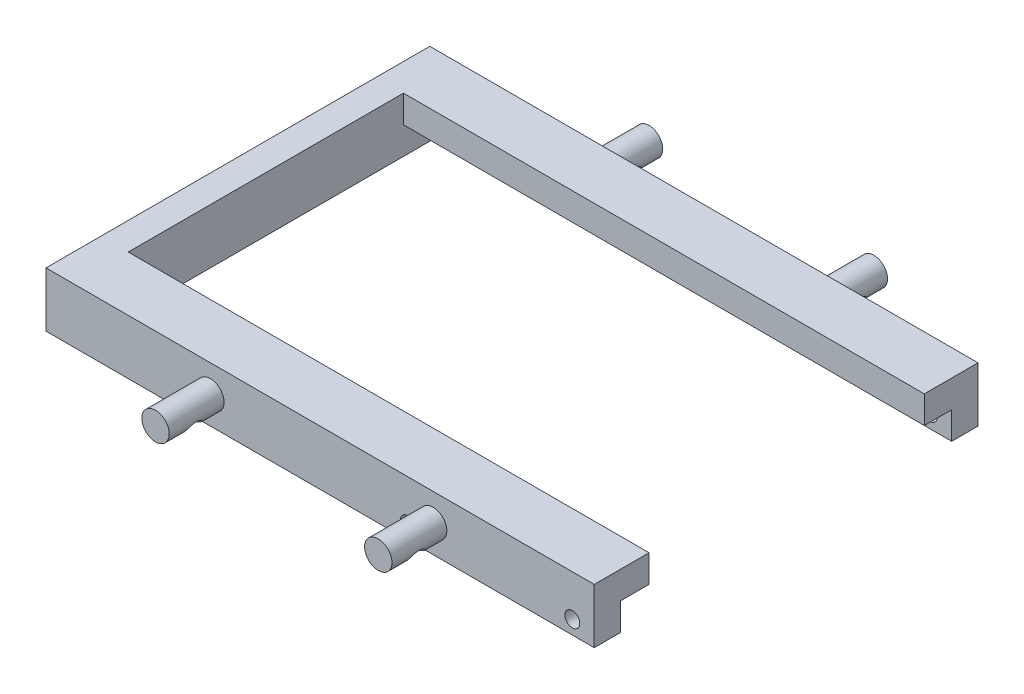
SolidWorks part; units mm, degrees
ref_plane "Front Plane" through (0, 0, 0) normal (0, 0, 1) x (1, 0, 0)
ref_plane "Top Plane" through (0, 0, 0) normal (0, 1, 0) x (1, 0, 0)
ref_plane "Right Plane" through (0, 0, 0) normal (1, 0, 0) x (0, 0, -1)
sketch "Sketch1" plane through (0, 0, 0) normal (0, 1, 0) x (1, 0, 0)
  line L1 (-76.2, 44.45) -> (-69.85, 44.45)
  line L2 (-76.2, 44.45) -> (-76.2, -44.45)
  line L3 (-76.2, -44.45) -> (-69.85, -44.45)
  line L4 (-69.85, 44.45) -> (-69.85, -44.45)
extrude "Boss-Extrude1" add sketch "Sketch1" along normal blind 6.35
sketch "Sketch2" plane through (-69.85, 0, 0) normal (1, 0, 0) x (0, 0, -1)
  line L0 (-44.45, 6.35) -> (-44.45, 0) construction
  line L1 (-44.45, 6.35) -> (-31.75, 6.35)
  line L2 (-44.45, 6.35) -> (-44.45, 0)
  line L3 (-44.45, 0) -> (-31.75, 0)
  line L4 (-31.75, 6.35) -> (-31.75, 0)
  line L5 (-44.45, 0) -> (44.45, 0) construction
extrude "Boss-Extrude2" add sketch "Sketch2" along normal blind 120.65
sketch "Sketch3" plane through (-69.85, 0, 0) normal (1, 0, 0) x (0, 0, -1)
  line L0 (-31.75, 0) -> (44.45, 0) construction
  line L1 (44.45, 6.35) -> (32.004, 6.35)
  line L2 (44.45, 6.35) -> (44.45, 0)
  line L3 (44.45, 0) -> (32.004, 0)
  line L4 (32.004, 6.35) -> (32.004, 0)
extrude "Boss-Extrude3" add sketch "Sketch3" along normal blind 120.65
extrude "Boss-Extrude4" add sketch "Sketch1<2>" against normal blind 6.35
sketch "Sketch1<2>" plane through (0, 0, 0) normal (0, 1, 0) x (1, 0, 0) same geometry as "Sketch1"
sketch "Sketch4" plane through (-69.85, 0, 0) normal (1, 0, 0) x (0, 0, -1)
  line L0 (-44.45, 0) -> (-31.75, 0) construction
  line L1 (-44.45, -6.35) -> (-38.354, -6.35)
  line L2 (-44.45, -6.35) -> (-44.45, 0)
  line L3 (-44.45, 0) -> (-38.354, 0)
  line L4 (-38.354, -6.35) -> (-38.354, 0)
extrude "Boss-Extrude5" add sketch "Sketch4" along normal blind 120.65
sketch "Sketch5" plane through (-69.85, 0, 0) normal (1, 0, 0) x (0, 0, -1)
  line L0 (32.004, 0) -> (44.45, 0) construction
  line L1 (44.45, -6.35) -> (38.354, -6.35)
  line L2 (44.45, -6.35) -> (44.45, 0)
  line L3 (44.45, 0) -> (38.354, 0)
  line L4 (38.354, -6.35) -> (38.354, 0)
extrude "Boss-Extrude6" add sketch "Sketch5" along normal blind 120.65
hole_wizard "#8-32 Tapped Hole1" positions "3DSketch2" profile "Sketch6" tap size "#8-32" standard "ANSI Inch" end condition up to next
sketch3d "3DSketch2"
  point P0 (45.72, -3.175, -44.45)
  point P2 (7.62, -3.175, -44.45)
  point P3 (45.72, -3.175, 44.45)
  point P5 (7.62, -3.175, 44.45)
sketch "Sketch6" plane through (45.72, -3.175, -44.45) normal (1, 0, 0) x (0, 1, 0)
  line L0 (0, 0) -> (0, 6.096)
  line L1 (0, 6.096) -> (1.7272, 6.096)
  line L2 (1.7272, 6.096) -> (1.7272, 0)
  line L5 (1.7272, 0) -> (0, 0)
  line L11 (0, -6.35) -> (0, 107.95) construction
  dimension "Thru Tap Drill Dia." = 3.4544
  dimension "Thru Tap Drill Depth" = 6.096
cosmetic thread "Hole Thread1" parameters "D2"=4.1656
cosmetic thread "Hole Thread2" parameters "D2"=4.1656
cosmetic thread "Hole Thread3" parameters "D2"=4.1656
cosmetic thread "Hole Thread4" parameters "D2"=4.1656
sketch "Sketch7" plane through (-14.4569, 0, 44.45) normal (0, 0, 1) x (1, 0, 0)
  circle A0 centre (27.94, 0) radius 3.175
extrude "Boss-Extrude7" add sketch "Sketch7" along normal blind 12.7
sketch "Sketch8" plane through (0, 0, 44.45) normal (0, 0, 1) x (1, 0, 0)
  circle A0 centre (-38.1291, 0) radius 3.175
extrude "Boss-Extrude8" add sketch "Sketch8" along normal blind 12.7
sketch "Sketch9" plane through (0, 0, -44.45) normal (0, 0, -1) x (-1, 0, 0)
  circle A0 centre (-13.97, 0) radius 3.175
  circle A1 centre (38.1, 0) radius 3.175
extrude "Boss-Extrude10" add sketch "Sketch9" along normal blind 12.7 contours A1
sketch "Sketch10" plane through (0, 0, -44.45) normal (0, 0, -1) x (-1, 0, 0)
  circle A0 centre (-13.97, 0) radius 3.175
extrude "Boss-Extrude11" add sketch "Sketch10" along normal blind 12.7
ref_plane "Plane2" through (17.145, 0, 0) normal (1, 0, 0) x (0, 0, -1)
sketch "Sketch12" plane through (17.145, 0, 0) normal (1, 0, 0) x (0, 0, -1)
  circle A0 centre (50.8, -3.048) radius 2.3812
extrude "Cut-Extrude2" cut sketch "Sketch12" against normal blind 127
sketch "Sketch13" plane through (17.145, 0, 0) normal (1, 0, 0) x (0, 0, -1)
  line L0 (-57.15, -3.175) -> (-44.45, -3.175) construction
  circle A0 centre (-50.8, -3.175) radius 2.3812
extrude "Cut-Extrude3" cut sketch "Sketch13" against normal blind 127
